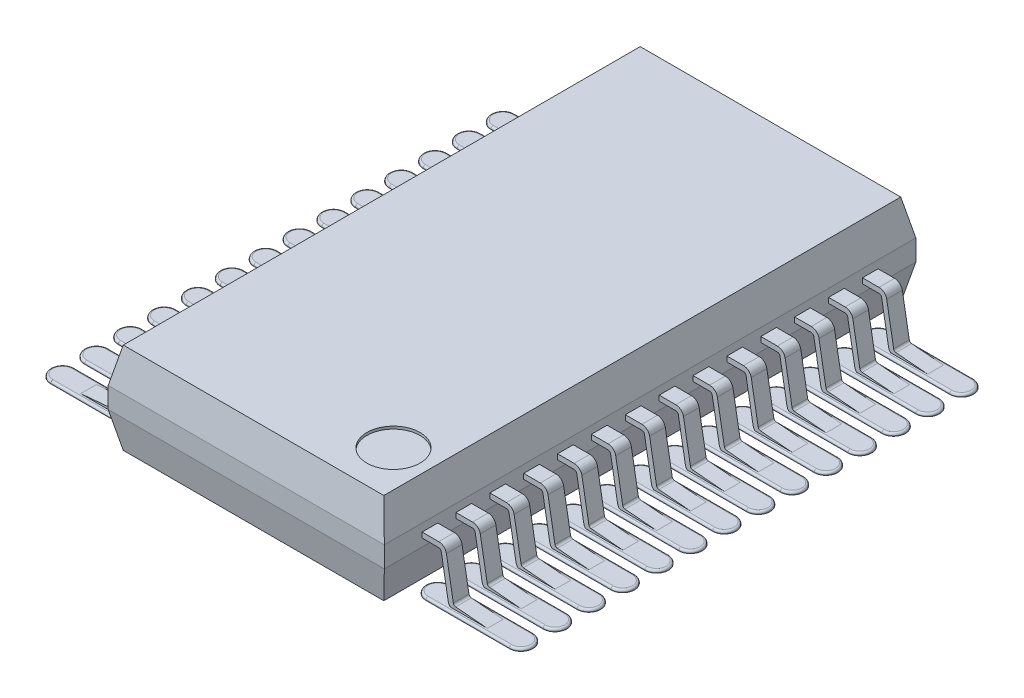
SolidWorks part; units mm, degrees
note: '?' marks a value the reader was unsure of.
material "普通碳钢"
ref_plane "Front Plane" through (0, 0, 0) normal (0, 0, 1) x (1, 0, 0)
ref_plane "Top Plane" through (0, 0, 0) normal (0, 1, 0) x (1, 0, 0)
ref_plane "Right Plane" through (0, 0, 0) normal (1, 0, 0) x (0, 0, -1)
ref_plane "Plane1" through (0, 0, 0) normal (0, 0, 1) x (1, 0, 0)
ref_plane "Plane5" through (0, 0, 4.225) normal (0, 0, 1) x (1, 0, 0)
sketch "Sketch1" plane through (0, 0, 0) normal (0, 0, 1) x (1, 0, 0)
  line L0 (-2.5, 1.85) -> (2.5, 1.85)
  line L1 (2.5, 0.1) -> (-2.5, 0.1)
  line L2 (-2.65, 0.975) -> (2.65, 0.975) construction
  line L3 (0, -55) -> (0, 55) construction
  line L4 (55, 0) -> (-55, 0) construction
  line L5 (-2.5, 1.85) -> (-2.65, 1.175)
  line L6 (-2.65, 1.175) -> (-2.65, 0.775)
  line L7 (-2.65, 0.775) -> (-2.5, 0.1)
  line L8 (2.5, 1.85) -> (2.65, 1.175)
  line L9 (2.65, 1.175) -> (2.65, 0.775)
  line L10 (2.65, 0.775) -> (2.5, 0.1)
  dimension "D5" = 0.4
  dimension "D1" = 1.75
  dimension "D2" = 5.3
  dimension "D3" = 2.65
  dimension "D4" = 0.1
  dimension "D6" = 5
  dimension "D7" = 2.5
  dimension "D8" = 0.15
extrude "Boss-Extrude1" add sketch "Sketch1" along normal mid plane 10.2
ref_plane "Plane2" through (0, 0, 4.445) normal (0, 0, 1) x (1, 0, 0)
sketch "Sketch4" plane through (0, 0, 0) normal (1, 0, 0) x (0, 0, -1)
  line L0 (-4.96, 1.85) -> (-5.1, 1.175)
  line L1 (-5.1, 1.85) -> (5.1, 1.85) construction
  line L2 (-5.1, 1.175) -> (-5.1, 0.775)
  line L3 (-5.1, 0.775) -> (-4.96, 0.1)
  line L4 (-5.1, 0.1) -> (5.1, 0.1) construction
  line L5 (-4.96, 0.1) -> (-5.16, 0.1)
  line L6 (-5.16, 0.1) -> (-5.16, 1.85)
  line L7 (-5.16, 1.85) -> (-4.96, 1.85)
  line L8 (5.1, 1.175) -> (4.96, 1.85)
  line L9 (4.96, 1.85) -> (5.16, 1.85)
  line L10 (5.16, 1.85) -> (5.16, 0.1)
  line L11 (5.16, 0.1) -> (4.96, 0.1)
  line L12 (4.96, 0.1) -> (5.1, 0.775)
  line L13 (5.1, 0.775) -> (5.1, 1.175)
  line L14 (5.1, 1.175) -> (5.1, 1.85) construction
  dimension "D1" = 0.14
  dimension "D2" = 0.2
  dimension "D3" = 0.2
  dimension "D4" = 0.14
extrude "Cut-Extrude2" cut sketch "Sketch4" against normal through all and the other way through all
sketch "Sketch2" plane through (0, 0, 4.225) normal (0, 0, 1) x (1, 0, 0)
  line L0 (3.0666, 0.8924) -> (3.2, 0.1356)
  line L1 (3.2898, 0.0534) -> (3.9, 0)
  line L2 (-3.0666, 0.8924) -> (-3.2, 0.1356)
  line L3 (-3.2898, 0.0534) -> (-3.9, 0)
  line L4 (2.9681, 0.975) -> (-2.9681, 0.975)
  line L9 (-2.5, 0.1) -> (2.5, 0.1) construction
  line L10 (2.915, 0) -> (-2.915, 0) construction
  line L11 (0, -0.9625) -> (0, 0.9625) construction
  arc A0 (3.0666, 0.8924) -> (2.9681, 0.975) centre (2.9681, 0.875) ccw
  arc A1 (3.2, 0.1356) -> (3.2898, 0.0534) centre (3.2985, 0.153) ccw
  arc A2 (-2.9681, 0.975) -> (-3.0666, 0.8924) centre (-2.9681, 0.875) ccw
  arc A3 (-3.2898, 0.0534) -> (-3.2, 0.1356) centre (-3.2985, 0.153) ccw
  dimension "D8" = 0.1
  dimension "D1" = 7.8
  dimension "D2" = 10
  dimension "D3" = 5
  dimension "D4" = 0.975
  dimension "D5" = 0.875
  dimension "D6" = 10
  dimension "D7" = 5
  dimension "D9" = 3.9
  dimension "D10" = 0.7
  dimension "D11" = 0.7
extrude "Extrude-Thin1" add sketch "Sketch2" along normal mid plane 0.3 thin thin type mid plane wall 0.1
ref_axis "Axis1" through (0, 0, 5.61) along (0, 0, -1)?
sketch "Sketch5" plane through (0, 0, 0) normal (0, 1, 0) x (1, 0, 0)
  line L0 (-2.8, -4.225) -> (-4.4, -4.225) construction
  line L1 (-1.4931, -4.225) -> (1.4931, -4.225) construction
  line L2 (-2.8, -4.45) -> (-4.4, -4.45)
  line L3 (-2.8, -4) -> (-4.4, -4)
  line L4 (2.8, -4.225) -> (4.4, -4.225) construction
  line L5 (2.8, -4) -> (4.4, -4)
  line L6 (2.8, -4.45) -> (4.4, -4.45)
  line L7 (0, -1.0449) -> (0, 1.0449) construction
  arc A0 (-2.8, -4.45) -> (-2.8, -4) centre (-2.8, -4.225) ccw
  arc A1 (-4.4, -4) -> (-4.4, -4.45) centre (-4.4, -4.225) ccw
  arc A2 (2.8, -4) -> (2.8, -4.45) centre (2.8, -4.225) ccw
  arc A3 (4.4, -4.45) -> (4.4, -4) centre (4.4, -4.225) ccw
  point P4 (-3.6, -4.225)
  point P9 (3.6, -4.225)
  dimension "D1" = 0.45
  dimension "D2" = 1.6
  dimension "D3" = 1.6
  dimension "D4" = 3.6
  dimension "D5" = 3.6
extrude "Boss-Extrude2" add sketch "Sketch5" along normal blind 0.05
fillet "Fillet1" radius 0.04 8 edges at (2.575, 0.05, 4.225) (3.6, 0.05, 4) (4.625, 0.05, 4.225) (-4.625, 0.05, 4.225) (-3.6, 0.05, 4) (-2.575, 0.05, 4.225) (3.6, 0.05, 4.45) (-3.6, 0.05, 4.45)
pattern_linear "LPattern1" count 14 spacing 0.65 along (0, 0, -1) of "Extrude-Thin1", "Boss-Extrude2", "Fillet1"
sketch "Sketch3" plane through (0, 1.85, 0) normal (0, 1, 0) x (-1, 0, 0)
  line L0 (0, 1.0449) -> (0, -1.0449) construction
  line L1 (1.4931, 4.225) -> (-1.4931, 4.225) construction
  circle A0 centre (-1.8, 4.075) radius 0.51
  dimension "D1" = 1.8
  dimension "D3" = 1.02
  dimension "D2" = 0.15
extrude "Cut-Extrude1" cut sketch "Sketch3" against normal blind 0.05
